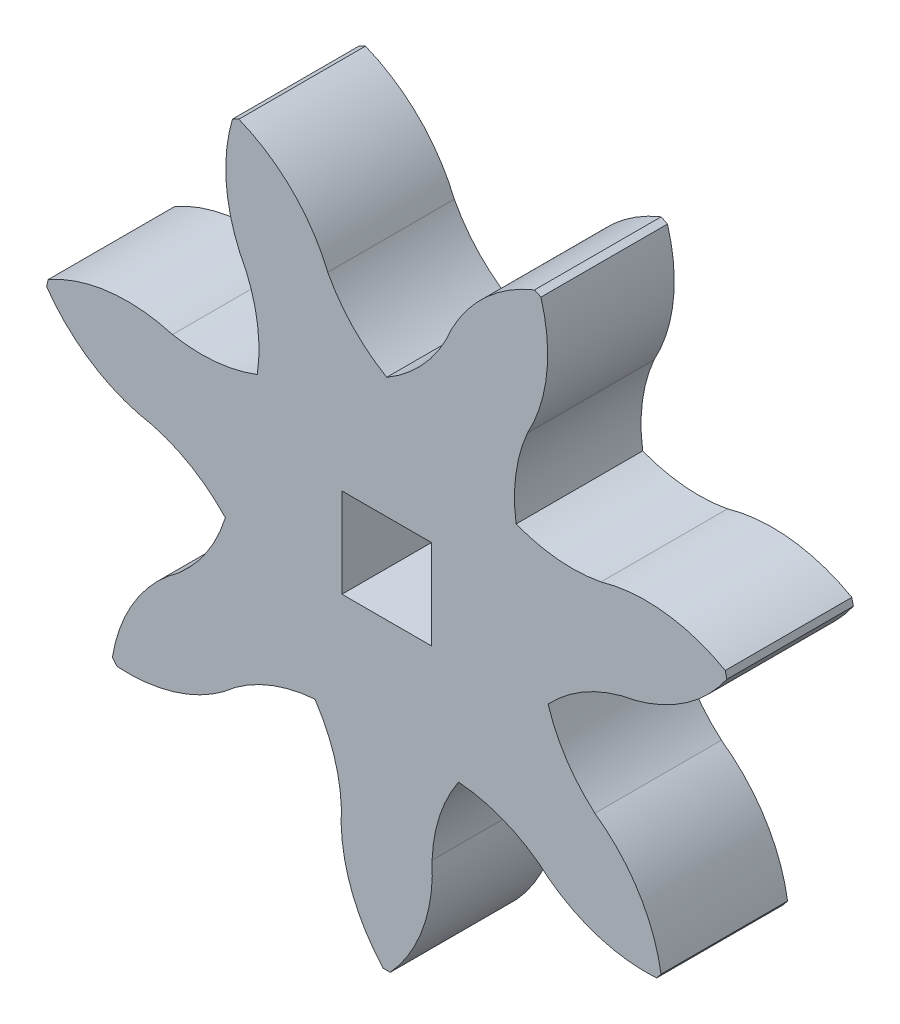
SolidWorks part; units mm, degrees
ref_plane "Front Plane" through (0, 0, 0) normal (0, 0, 1) x (1, 0, 0)
ref_plane "Top Plane" through (0, 0, 0) normal (0, 1, 0) x (1, 0, 0)
ref_plane "Right Plane" through (0, 0, 0) normal (1, 0, 0) x (0, 0, -1)
sketch "Sketch1" plane through (0, 0, 0) normal (0, 0, 1) x (1, 0, 0)
  line L1 (3.5355, -3.5355) -> (-3.5355, -3.5355)
  line L2 (3.5355, -3.5355) -> (3.5355, 3.5355)
  line L3 (3.5355, 3.5355) -> (-3.5355, 3.5355)
  line L4 (-3.5355, -3.5355) -> (-3.5355, 3.5355)
  line L5 (3.5355, -3.5355) -> (-3.5355, 3.5355) construction
  line L6 (3.5355, 3.5355) -> (-3.5355, -3.5355) construction
  circle A0 centre (0, 0) radius 27.5
  circle A1 centre (0, 0) radius 5 construction
  dimension "D1" = 55
  dimension "D2" = 10
extrude "Boss-Extrude1" add sketch "Sketch1" along normal blind 10
sketch "Sketch2" plane through (0, 0, 0) normal (0, 0, 1) x (1, 0, 0)
  line L1 (0, 0) -> (0, 35.1158) construction
  arc A8 (-12.0857, 25.0526) -> (0, 35.1158) centre (1.2487, 21.3272) cw
  arc A12 (-12.0857, 25.0526) -> (-4.6585, 17.9328) centre (-16.4393, 13.0772) cw
  arc A13 (-4.6585, 17.9328) -> (0, 13.0772) centre (6.1453, 23.6356) ccw
  arc A14 (4.6585, 17.9328) -> (0, 13.0772) centre (-6.1453, 23.6356) cw
  arc A15 (12.0857, 25.0526) -> (4.6585, 17.9328) centre (16.4393, 13.0772) ccw
  arc A16 (12.0857, 25.0526) -> (0, 35.1158) centre (-1.2487, 21.3272) ccw
extrude "Cut-Extrude1" cut sketch "Sketch2" along normal through all
pattern_circular "CirPattern1" count 7 over 360 about axis through (0, 0, 10) along (0, 0, -1) of "Cut-Extrude1"
